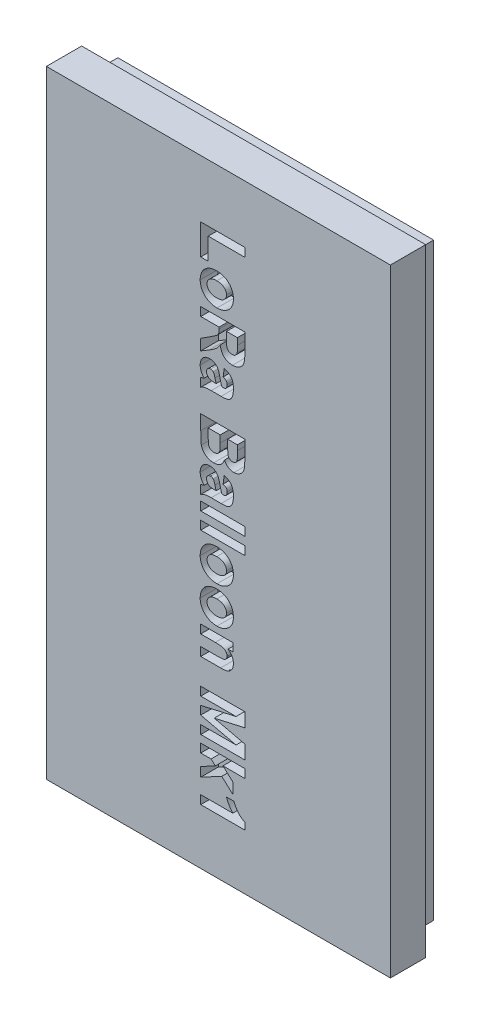
SolidWorks part; units mm, degrees
ref_plane "Front Plane" through (0, 0, 0) normal (0, 0, 1) x (1, 0, 0)
ref_plane "Top Plane" through (0, 0, 0) normal (0, 1, 0) x (1, 0, 0)
ref_plane "Right Plane" through (0, 0, 0) normal (1, 0, 0) x (0, 0, -1)
sketch "Sketch1" plane through (0, 0, 0) normal (0, 0, 1) x (1, 0, 0)
  line L1 (0, 0) -> (39, 0)
  line L2 (0, 0) -> (0, 70)
  line L3 (0, 70) -> (39, 70)
  line L4 (39, 0) -> (39, 70)
  dimension "D1" = 70
  dimension "D2" = 39
extrude "Boss-Extrude1" add sketch "Sketch1" along normal blind 4
sketch "Sketch2" plane through (0, 0, 0) normal (0, 0, -1) x (-1, 0, 0)
  line L0 (-39, 0) -> (-39, 70) construction
  line L1 (-37.4, 68.4) -> (-35.6, 68.4)
  line L2 (-37.4, 68.4) -> (-37.4, 1.6)
  line L3 (-37.4, 1.6) -> (-35.6, 1.6)
  line L4 (-35.6, 68.4) -> (-35.6, 1.6)
  line L5 (0, 0) -> (-39, 0) construction
  line L6 (0, 70) -> (0, 0) construction
  line L7 (-35.6, 1.6) -> (-1.6, 1.6)
  line L8 (-35.6, 1.6) -> (-35.6, 3.4)
  line L9 (-35.6, 3.4) -> (-1.6, 3.4)
  line L10 (-1.6, 1.6) -> (-1.6, 3.4)
  line L12 (-39, 70) -> (0, 70) construction
  line L13 (-39, 35) -> (0, 35) construction
  line L14 (-19.5, 70) -> (-19.5, 0) construction
  line L15 (-35.6, 66.6) -> (-1.6, 66.6)
  line L16 (-1.6, 68.4) -> (-1.6, 66.6)
  line L17 (-35.6, 68.4) -> (-1.6, 68.4)
  line L18 (-35.6, 68.4) -> (-35.6, 66.6)
  line L19 (-1.6, 1.6) -> (-3.4, 1.6)
  line L20 (-3.4, 68.4) -> (-3.4, 1.6)
  line L21 (-1.6, 68.4) -> (-3.4, 68.4)
  line L22 (-1.6, 68.4) -> (-1.6, 1.6)
  dimension "D1" = 1.6
  dimension "D2" = 1.8
  dimension "D3" = 1.6
  dimension "D4" = 1.8
extrude "Boss-Extrude2" add sketch "Sketch2" along normal blind 2.5 contours L4 L1 L2 L3 | L22 L15 L20 L9 | L20 L9 L4 L7 | L9 L20 L7 L10 | L17 L20 L15 L16 | L20 L17 L4 L15 region at (36.5, 35, 0) region at (19.5, 67.5, 0) region at (2.5, 67.5, 0) region at (19.5, 2.5, 0) region at (2.5, 35, 0) region at (2.5, 2.5, 0)
sketch "Sketch3" plane through (0, 0, 4) normal (0, 0, 1) x (1, 0, 0)
  line L0 (17.5, 0) -> (17.5, 64) construction
  line L4 (0, 0) -> (39, 0) construction
  line L6 (0, 70) -> (0, 0) construction
  text T0 "<b>LoRa Balloon Mk1</b>" font "Arial Narrow" height 5
  dimension "D1" = 17.5
  dimension "D2" = 64
extrude "Cut-Extrude1" cut sketch "Sketch3" against normal blind 2
